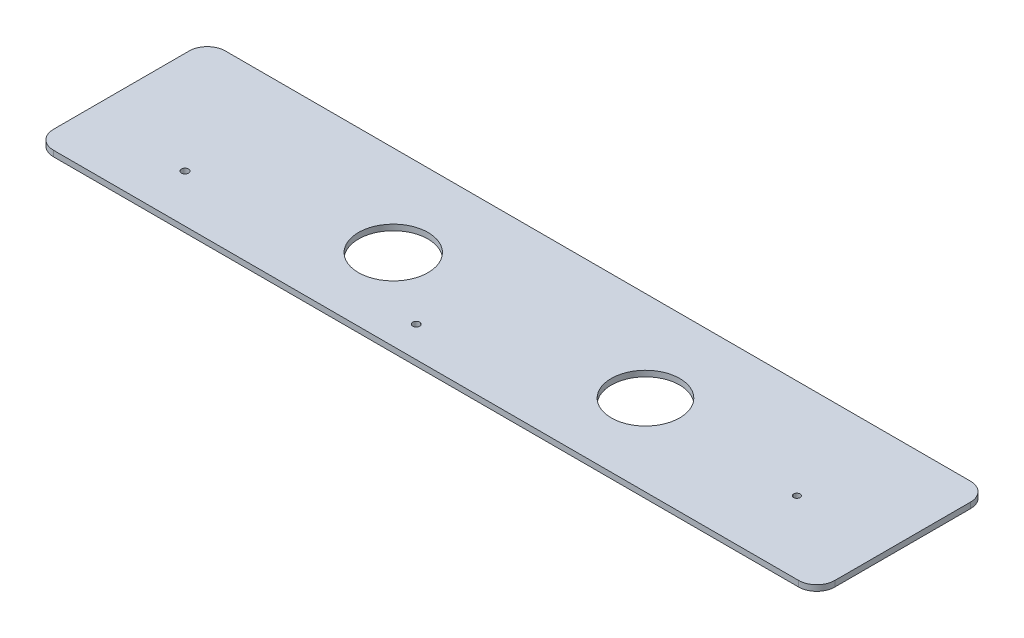
SolidWorks part; units mm, degrees
ref_plane "Front" through (0, 0, 0) normal (0, 0, 1) x (1, 0, 0)
ref_plane "Top" through (0, 0, 0) normal (0, 1, 0) x (1, 0, 0)
ref_plane "Right" through (0, 0, 0) normal (1, 0, 0) x (0, 0, -1)
sketch "Sketch1" plane through (0, 0, 0) normal (0, 1, 0) x (1, 0, 0)
  line L1 (-2.1325, 0) -> (429.6675, 0)
  line L2 (-2.1325, 0) -> (-2.1325, 95)
  line L3 (-2.1325, 95) -> (429.6675, 95)
  line L4 (429.6675, 0) -> (429.6675, 95)
  circle A0 centre (54.1918, 26.3683) radius 2
  circle A1 centre (191.3656, 16.9951) radius 1.9494
  circle A2 centre (150.7358, 44.9163) radius 19.2353
  circle A3 centre (290.117, 44.9123) radius 18.8981
  circle A4 centre (378.6675, 40.0503) radius 1.7702
  dimension "D1" = 95
  dimension "D2" = 431.8
extrude "Boss-Extrude1" add sketch "Sketch1" along normal blind 3.175
fillet "Fillet1" radius 10 4 edges at (429.6675, 1.5875, -95) (429.6675, 1.5875, 0) (-2.1325, 1.5875, 0) (-2.1325, 1.5875, -95)
